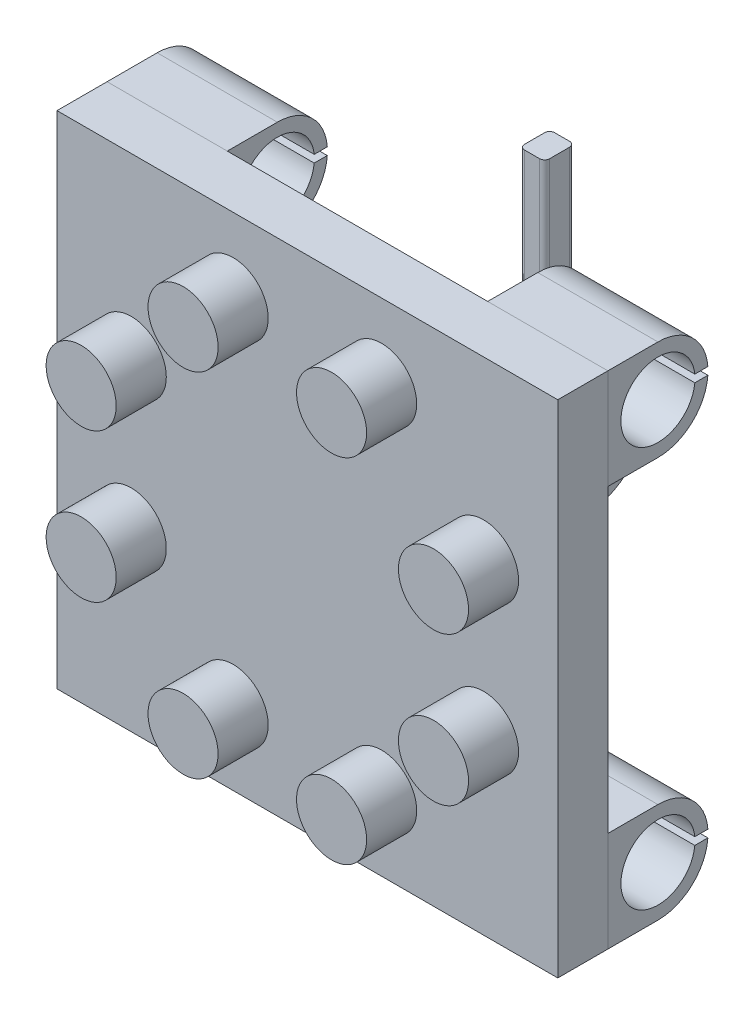
SolidWorks part; units mm, degrees
ref_plane "Plano frontal" through (0, 0, 0) normal (0, 0, 1) x (1, 0, 0)
ref_plane "Plano superior" through (0, 0, 0) normal (0, 1, 0) x (1, 0, 0)
ref_plane "Plano direito" through (0, 0, 0) normal (1, 0, 0) x (0, 0, -1)
sketch "Esboço1" plane through (0, 0, 0) normal (0, 0, 1) x (1, 0, 0)
  line L1 (-25.8743, 34.174) -> (-25.8743, -39.4705) construction
  line L2 (-25.8743, 21.9595) -> (37.4155, 21.9595) construction
  line L3 (24.1257, -28.0405) -> (24.1257, 21.9595) construction
  line L4 (-25.8743, 21.9595) -> (-11.0487, 7.134) construction
  line L5 (-11.0487, 7.134) -> (9.3002, -13.2149) construction
  line L6 (9.3002, -13.2149) -> (24.1257, -28.0405) construction
  line L7 (-25.8743, -28.0405) -> (24.1257, 21.9595) construction
  line L9 (-25.8743, 21.9595) -> (24.1257, 21.9595)
  line L10 (-25.8743, 21.9595) -> (-25.8743, -28.0405)
  line L11 (-25.8743, -28.0405) -> (24.1257, -28.0405)
  line L12 (24.1257, 21.9595) -> (24.1257, -28.0405)
  dimension "D1" = 50
extrude "Ressalto-extrusão1" add sketch "Esboço1" along normal blind 10
sketch "Esboço2" plane through (0, 0, 10) normal (0, 0, 1) x (1, 0, 0)
  line L0 (-25.8743, -28.0405) -> (27.247, -28.0405) construction
  line L1 (-11.0487, 21.9595) -> (-11.0487, -28.0405) construction
  line L2 (24.1257, 21.9595) -> (-25.8743, 21.9595) construction
  line L3 (9.3002, 21.9595) -> (9.3002, -28.0405) construction
  line L4 (-25.8743, -28.0405) -> (-25.8743, 21.9595) construction
  line L5 (-25.8743, 7.134) -> (24.1257, 7.134) construction
  line L6 (24.1257, -28.0405) -> (24.1257, 21.9595) construction
  line L7 (-25.8743, -13.2149) -> (24.1257, -13.2149) construction
  circle A0 centre (-11.0487, 7.134) radius 7
  circle A3 centre (9.3002, -13.2149) radius 7
extrude "Ressalto-extrusão2" add sketch "Esboço2" along normal blind 10
mirror "Espelhar11" about plane through (-25.8743, 21.9595, 10) normal (1, 0, 0) of "Ressalto-extrusão2", "Ressalto-extrusão1"
mirror "Espelhar12" about plane through (-25.8743, -28.0405, 10) normal (0, 1, 0) of "Ressalto-extrusão2", "Ressalto-extrusão1"
mirror "Espelhar13" about plane through (-25.8743, -78.0405, 10) normal (-1, 0, 0) of "Espelhar12"
sketch "Esboço3" plane through (0, 0, 0) normal (0, 0, -1) x (-1, 0, 0)
  line L2 (-24.1257, -78.0405) -> (-0.1257, -78.0405)
  line L5 (-24.1257, -78.0405) -> (-24.1257, -58.0405)
  line L31 (-24.1257, -58.0405) -> (-0.1257, -58.0405)
  line L35 (-0.1257, -78.0405) -> (-0.1257, -58.0405)
  line L41 (51.8743, -78.0405) -> (75.8743, -78.0405)
  line L54 (51.8743, -78.0405) -> (51.8743, -58.0405)
  line L55 (51.8743, -58.0405) -> (75.8743, -58.0405)
  line L56 (75.8743, -78.0405) -> (75.8743, -58.0405)
  line L57 (51.8743, 1.9595) -> (75.8743, 1.9595)
  line L58 (51.8743, 1.9595) -> (51.8743, 21.9595)
  line L59 (51.8743, 21.9595) -> (75.8743, 21.9595)
  line L60 (75.8743, 1.9595) -> (75.8743, 21.9595)
  line L61 (-24.1257, 1.9595) -> (-0.1257, 1.9595)
  line L62 (-24.1257, 1.9595) -> (-24.1257, 21.9595)
  line L63 (-24.1257, 21.9595) -> (-0.1257, 21.9595)
  line L64 (-0.1257, 1.9595) -> (-0.1257, 21.9595)
  dimension "D1" = 24
  dimension "D2" = 20
extrude "Ressalto-extrusão3" add sketch "Esboço3" along normal blind 20 separate body
fillet "Filete3" radius 10 2 edges at (12.1257, -58.0405, -20) (12.1257, -78.0405, -20)
fillet "Filete4" radius 10 2 edges at (-63.8743, -58.0405, -20) (-63.8743, -78.0405, -20)
fillet "Filete5" radius 10 2 edges at (12.1257, 21.9595, -20) (12.1257, 1.9595, -20)
fillet "Filete6" radius 10 2 edges at (-63.8743, 21.9595, -20) (-63.8743, 1.9595, -20)
sketch "Esboço4" plane through (24.1257, 0, 0) normal (1, 0, 0) x (0, 0, -1)
  line L0 (20, -68.0405) -> (17.4, -68.0405) construction
  line L1 (0, -58.0405) -> (0, -78.0405) construction
  line L2 (10, -78.0405) -> (10, -58.0405) construction
  line L3 (10, 1.9595) -> (10, 21.9595) construction
  line L4 (20, 11.9595) -> (0, 11.9595) construction
  line L5 (0, 21.9595) -> (0, 1.9595) construction
  line L6 (16.8497, -68.0405) -> (0, -68.0405) construction
  line L11 (20.3514, -68.7905) -> (17.3619, -68.7905)
  line L12 (20.3514, -68.7905) -> (20.3514, -67.2905)
  line L13 (20.3514, -67.2905) -> (17.3619, -67.2905)
  line L15 (20.3514, 11.2095) -> (17.3619, 11.2095)
  line L16 (20.3514, 11.2095) -> (20.3514, 12.7095)
  line L17 (20.3514, 12.7095) -> (17.3619, 12.7095)
  arc A0 (17.3619, -67.2905) -> (17.3619, -68.7905) centre (10, -68.0405) ccw
  arc A2 (17.3619, 12.7095) -> (17.3619, 11.2095) centre (10, 11.9595) ccw
  point P25 (10, 11.9595)
  dimension "D1" = 14.8
  dimension "D2" = 1.5
extrude "Corte-extrusão1" cut sketch "Esboço4" against normal through all both and the other way through all
sketch "Esboço5" plane through (0, 0, 0) normal (0, 0, -1) x (-1, 0, 0)
  line L0 (75.8743, -28.0405) -> (-24.1257, -28.0405) construction
  line L1 (75.8743, -78.0405) -> (75.8743, 21.9595) construction
  line L2 (-24.1257, -78.0405) -> (-24.1257, 21.9595) construction
  line L3 (25.8743, -78.0405) -> (25.8743, 21.9595) construction
  line L4 (-24.1257, -78.0405) -> (75.8743, -78.0405) construction
  line L5 (-24.1257, 21.9595) -> (75.8743, 21.9595) construction
  line L6 (43.3743, -28.0405) -> (8.3743, -28.0405) construction
  line L7 (43.3743, -43.0405) -> (8.3743, -43.0405)
  line L8 (43.3743, -43.0405) -> (43.3743, -13.0405)
  line L9 (43.3743, -13.0405) -> (8.3743, -13.0405)
  line L10 (8.3743, -43.0405) -> (8.3743, -13.0405)
  line L11 (25.8743, -43.0405) -> (25.8743, -13.0405) construction
  point P20 (25.8743, -28.0405)
  point P21 (25.8743, -28.0405)
  dimension "D1" = 35
  dimension "D2" = 30
extrude "Ressalto-extrusão4" add sketch "Esboço5" along normal blind 50
sketch "Esboço6" plane through (-43.3743, 0, 0) normal (-1, 0, 0) x (0, 0, 1)
  line L0 (-50, -28.0405) -> (0, -28.0405) construction
  line L1 (-50, -43.0405) -> (-50, -13.0405) construction
  line L2 (0, -78.0405) -> (0, 21.9595) construction
  line L3 (-25, -43.0405) -> (-25, -13.0405) construction
  line L4 (-50, -43.0405) -> (0, -43.0405) construction
  line L5 (-50, -13.0405) -> (0, -13.0405) construction
  line L6 (-25, -43.0405) -> (-50, -13.0405) construction
  line L7 (-25, -13.0405) -> (-50, -43.0405) construction
  circle A0 centre (-37.5, -28.0405) radius 11.5
  dimension "D1" = 23
sketch "Esboço7" plane through (0, -43.0405, 0) normal (0, -1, 0) x (1, 0, 0)
  line L0 (-25.8743, -50) -> (-25.8743, 0) construction
  line L1 (-8.3743, -50) -> (-43.3743, -50) construction
  line L2 (-8.3743, 0) -> (-43.3743, 0) construction
  line L3 (-25.8743, -50) -> (-32.8743, -50) construction
  line L4 (-25.8743, -50) -> (-18.8743, -50) construction
  line L5 (-8.3743, 0) -> (-8.3743, -50)
  line L6 (-18.8743, -50) -> (-8.3743, -50)
  line L7 (-43.3743, 0) -> (-43.3743, -50)
  line L8 (-32.8743, -50) -> (-43.3743, -50)
  arc A0 (-32.8743, -50) -> (-43.3743, 0) centre (-157.1719, -50) ccw
  arc A1 (-18.8743, -50) -> (-8.3743, 0) centre (105.4234, -50) cw
extrude "Corte-extrusão2" cut sketch "Esboço7" against normal through all both and the other way through all
extrude "Corte-extrusão3" cut sketch "Esboço6" against normal blind 15
sketch "Esboço8" plane through (-28.3743, 0, 0) normal (-1, 0, 0) x (0, 0, 1)
  circle A0 centre (-37.5, -28.0405) radius 5.25
  circle A1 centre (-37.5, -28.0405) radius 11.5 construction
  dimension "D1" = 10.5
extrude "Corte-extrusão4" cut sketch "Esboço8" against normal through all
fillet "Filete7" radius 10 2 edges at (-25.8743, -13.0405, -50) (-25.8743, -43.0405, -50)
sketch "Esboço9" plane through (0, -13.0405, 0) normal (0, 1, 0) x (1, 0, 0)
  line L0 (-137.5433, 37.8701) -> (-15.7518, 37.8701) construction
  line L1 (-27.3743, 40.8701) -> (-24.3743, 40.8701)
  line L2 (-28.3743, 39.8701) -> (-28.3743, 35.8701)
  line L3 (-27.3743, 34.8701) -> (-24.3743, 34.8701)
  line L4 (-23.3743, 39.8701) -> (-23.3743, 35.8701)
  line L5 (-28.3743, 37.8701) -> (-23.3743, 37.8701) construction
  line L6 (-25.8743, 50) -> (-25.8743, 23.4143) construction
  line L7 (-32.8743, 50) -> (-18.8743, 50) construction
  line L8 (-25.8743, 40.8701) -> (-25.8743, 34.8701) construction
  arc A0 (-28.3743, 35.8701) -> (-27.3743, 34.8701) centre (-27.3743, 35.8701) ccw
  arc A1 (-24.3743, 34.8701) -> (-23.3743, 35.8701) centre (-24.3743, 35.8701) ccw
  arc A2 (-24.3743, 40.8701) -> (-23.3743, 39.8701) centre (-24.3743, 39.8701) cw
  arc A3 (-27.3743, 40.8701) -> (-28.3743, 39.8701) centre (-27.3743, 39.8701) ccw
  point P19 (-23.3743, 34.8701)
  point P22 (-23.3743, 40.8701)
  point P25 (-28.3743, 40.8701)
  dimension "D3" = 1
  dimension "D1" = 5
  dimension "D2" = 6
extrude "Ressalto-extrusão5" add sketch "Esboço9" along normal blind 30
